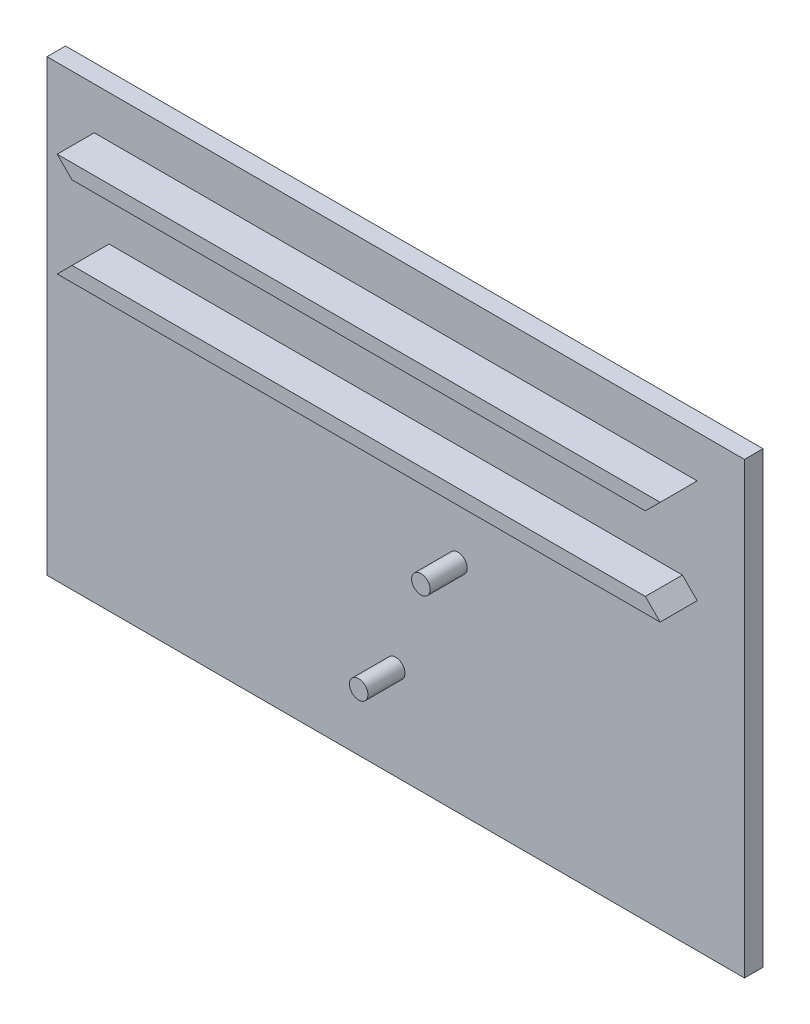
SolidWorks part; units mm, degrees
ref_plane "Front Plane" through (0, 0, 0) normal (0, 0, 1) x (1, 0, 0)
ref_plane "Top Plane" through (0, 0, 0) normal (0, 1, 0) x (1, 0, 0)
ref_plane "Right Plane" through (0, 0, 0) normal (1, 0, 0) x (0, 0, -1)
sketch "Sketch2" plane through (0, 0, 0) normal (0, 0, 1) x (1, 0, 0)
  line L0 (0, 0) -> (0, 89.408) construction
  line L1 (0, 0) -> (21.333, 41.8684) construction
  line L2 (0, 0) -> (53.1814, 0) construction
  line L3 (-98.2512, 102.108) -> (98.2512, 102.108)
  line L5 (-98.2512, 76.708) -> (98.2512, 76.708)
  line L7 (-98.2512, 102.108) -> (98.2512, 76.708) construction
  line L8 (-98.2512, 76.708) -> (98.2512, 102.108) construction
  line L9 (-103.3312, 71.628) -> (103.3312, 71.628)
  line L11 (-103.3312, 107.188) -> (103.3312, 107.188)
  line L13 (-98.2512, 102.108) -> (-98.2512, 76.708) construction
  line L14 (-103.3312, 107.188) -> (-103.3312, 71.628) construction
  line L15 (98.2512, 102.108) -> (98.2512, 76.708) construction
  line L16 (103.3312, 107.188) -> (103.3312, 71.628) construction
  line L17 (-103.3312, 71.628) -> (-98.2512, 76.708)
  line L18 (-103.3312, 107.188) -> (-98.2512, 102.108)
  line L19 (103.3312, 107.188) -> (98.2512, 102.108)
  line L20 (98.2512, 102.108) -> (98.2512, 76.708)
  line L21 (103.3312, 71.628) -> (98.2512, 76.708)
  line L23 (-119.5322, 121.6741) -> (119.5322, 121.6741)
  line L24 (-119.5322, 121.6741) -> (-119.5322, -32.2661)
  line L25 (-119.5322, -32.2661) -> (119.5322, -32.2661)
  line L26 (119.5322, 121.6741) -> (119.5322, -32.2661)
  line L27 (-119.5322, 121.6741) -> (119.5322, -32.2661) construction
  line L28 (-119.5322, -32.2661) -> (119.5322, 121.6741) construction
  circle A0 centre (0, 0) radius 3.175
  circle A1 centre (21.333, 41.8684) radius 3.175
  point P15 (0, 44.704)
  dimension "D6" = 6.35
  dimension "D7" = 6.35
  dimension "D1" = 89.408
  dimension "D2" = 46.99
  dimension "D3" = 63
  dimension "D4" = 25.4
  dimension "D8" = 153.9403
  dimension "D9" = 239.0644
  dimension "D10" = 196.5024
  dimension "D5" = 5.08
extrude "Boss-Extrude1" add sketch "Sketch2" along normal blind 12.7 contours A1 | A0 | L3 L18 L11 L19 | L21 L9 L17 L5 region at (0, 0, 0) region at (21.333, 41.8684, 0)
extrude "Boss-Extrude2" add sketch "Sketch2<3>" against normal blind 6.35 contours L24 L25 L26 L23
sketch "Sketch2<3>" plane through (0, 0, 0) normal (0, 0, 1) x (1, 0, 0) same geometry as "Sketch2"
